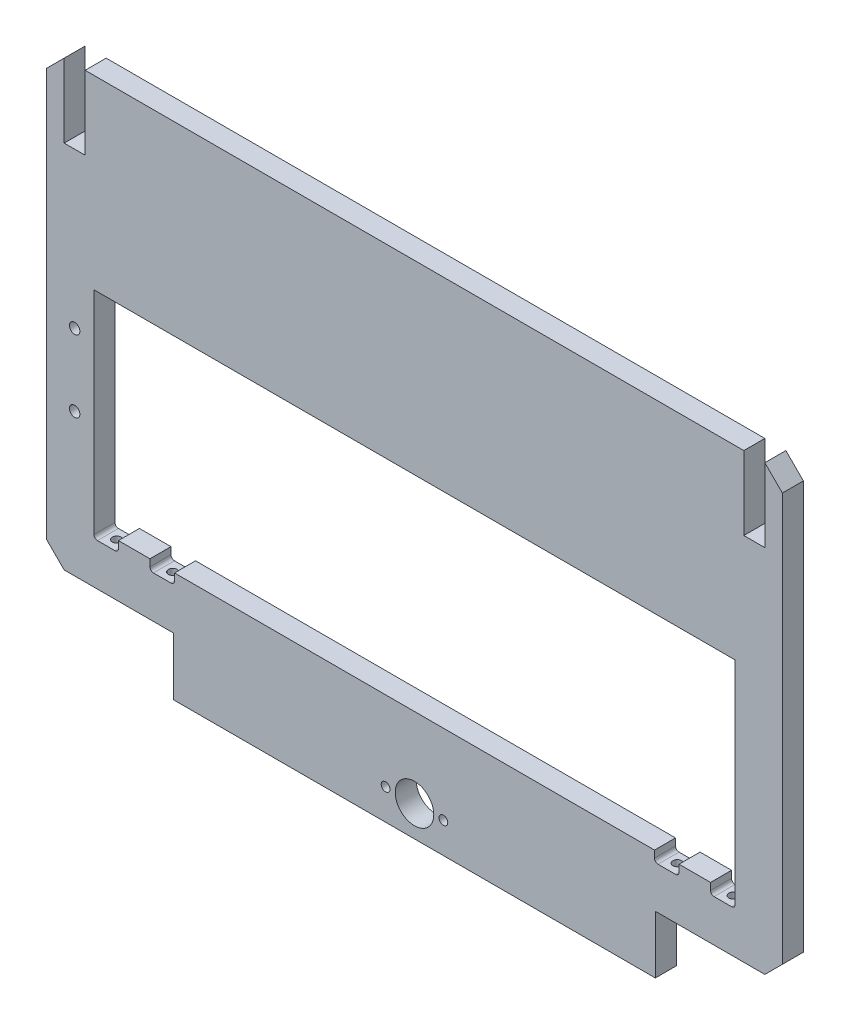
SolidWorks part; units mm, degrees
other "DetailItem1"
other "DetailItem2"
material "Beech"
ref_plane "Front Plane" through (0, 0, 0) normal (0, 0, 1) x (1, 0, 0)
ref_plane "Top Plane" through (0, 0, 0) normal (0, 1, 0) x (1, 0, 0)
ref_plane "Right Plane" through (0, 0, 0) normal (1, 0, 0) x (0, 0, -1)
sketch "Sketch1" plane through (0, 0, 0) normal (0, 0, 1) x (1, 0, 0)
  line L1 (-137.5, -16.5) -> (137.5, -16.5)
  line L2 (-137.5, -16.5) -> (-137.5, 16.5)
  line L3 (-137.5, 16.5) -> (137.5, 16.5)
  line L4 (137.5, -16.5) -> (137.5, 16.5)
  line L5 (-137.5, -16.5) -> (137.5, 16.5) construction
  line L6 (-137.5, 16.5) -> (137.5, -16.5) construction
  point P0 (0, 0)
  dimension "D1" = 275
  dimension "D2" = 33
extrude "Boss-Extrude1" add sketch "Sketch1" along normal blind 12
sketch "Sketch2" plane through (0, 0, 12) normal (0, 0, 1) x (1, 0, 0)
  line L0 (137.5, 16.5) -> (-137.5, 16.5) construction
  line L1 (-16.5, 1) -> (20.0379, 1) construction
  circle A0 centre (0, 1) radius 11
  circle A1 centre (-16.5, 1) radius 2.5
  circle A2 centre (16.5, 1) radius 2.5
  point P2 (0, 16.5)
  dimension "D1" = 15.5
  dimension "D2" = 22
  dimension "D3" = 5
  dimension "D4" = 5
  dimension "D5" = 33
  dimension "D6" = 16.5
extrude "Cut-Extrude1" cut sketch "Sketch2" against normal up to next
sketch "Sketch3" plane through (0, 0, 12) normal (0, 0, 1) x (1, 0, 0)
  line L0 (-137.5, -16.5) -> (137.5, -16.5) construction
  line L1 (-210, 16.5) -> (210, 16.5)
  line L2 (-210, 16.5) -> (-210, 46.5)
  line L3 (-183, 46.5) -> (183, 46.5)
  line L4 (210, 16.5) -> (210, 46.5)
  line L5 (-183, 163.5) -> (183, 163.5)
  line L6 (-210, 46.5) -> (-210, 269.5)
  line L7 (-210, 269.5) -> (210, 269.5)
  line L8 (-183, 46.5) -> (-183, 163.5)
  line L11 (210, 46.5) -> (210, 269.5)
  line L13 (183, 46.5) -> (183, 163.5)
  circle A0 centre (0, 1) radius 11 construction
  dimension "D1" = 30
  dimension "D2" = 420
  dimension "D3" = 210
  dimension "D5" = 286
  dimension "D8" = 117
extrude "Boss-Extrude2" add sketch "Sketch3" against normal blind 12
sketch "Sketch4" plane through (0, 46.5, 0) normal (0, 1, 0) x (1, 0, 0)
  line L0 (-183, -6) -> (183, -6) construction
  line L1 (-183, 0) -> (-183, -12) construction
  line L2 (183, 0) -> (183, -12) construction
  line L4 (183, 0) -> (-183, 0) construction
  circle A0 centre (-144, -6) radius 2.5
  circle A1 centre (-176, -6) radius 2.5
  point P10 (0, 0)
  point P12 (0, 0)
  dimension "D1" = 5
  dimension "D2" = 5
  dimension "D3" = 144
  dimension "D4" = 176
extrude "Cut-Extrude2" cut sketch "Sketch4" against normal up to next
mirror "Mirror1" about plane through (0, 0, 0) normal (1, 0, 0) of "Cut-Extrude2"
sketch "Sketch5" plane through (0, 0, 12) normal (0, 0, 1) x (1, 0, 0)
  line L0 (-183, 46.5) -> (-183, 40.5)
  line L1 (-183, 40.5) -> (-169, 40.5)
  line L2 (-169, 40.5) -> (-169, 46.5)
  line L3 (183, 46.5) -> (-183, 46.5) construction
  line L4 (-169, 46.5) -> (-183, 46.5)
  line L5 (-151, 46.5) -> (-151, 40.5)
  line L6 (-151, 40.5) -> (-137, 40.5)
  line L7 (-137, 40.5) -> (-137, 46.5)
  line L8 (-151, 46.5) -> (-137, 46.5)
  circle A0 centre (0, 1) radius 11 construction
  dimension "D1" = 14
  dimension "D2" = 6
  dimension "D3" = 6
  dimension "D4" = 14
  dimension "D5" = 137
  dimension "D6" = 169
extrude "Cut-Extrude3" cut sketch "Sketch5" against normal up to next
fillet "Fillet1" radius 2 4 edges at (-137, 40.5, 6) (-151, 40.5, 6) (-169, 40.5, 6) (-183, 40.5, 6)
mirror "Mirror2" about plane through (0, 0, 0) normal (1, 0, 0) of "Fillet1", "Cut-Extrude3"
chamfer "Chamfer1" distance 10 angle 45 2 edges at (210, 16.5, 6) (-210, 16.5, 6)
sketch "Sketch6" plane through (0, 0, 12) normal (0, 0, 1) x (1, 0, 0)
  line L0 (-194, 84.613) -> (-194, 177.9433) construction
  line L1 (194, 84.613) -> (194, 173.992) construction
  line L3 (-183, 42.5) -> (-183, 163.5) construction
  line L4 (183, 163.5) -> (183, 42.5) construction
  circle A0 centre (-194, 138.9056) radius 3
  circle A1 centre (-194, 97.8948) radius 3
  dimension "D3" = 6
  dimension "D4" = 6
  dimension "D1" = 11
  dimension "D2" = 11
extrude "Cut-Extrude4" cut sketch "Sketch6" against normal up to next
sketch "Sketch8" plane through (0, 0, 12) normal (0, 0, 1) x (1, 0, 0)
  line L0 (0, 79.2288) -> (0, 236.3795) construction
  line L1 (210, 269.5) -> (-210, 269.5) construction
  line L2 (-188, 269.5) -> (-200, 269.5)
  line L3 (-188, 269.5) -> (-188, 227.5)
  line L4 (-188, 227.5) -> (-200, 227.5)
  line L5 (-200, 269.5) -> (-200, 227.5)
  line L7 (188, 269.5) -> (200, 269.5)
  line L8 (188, 269.5) -> (188, 227.5)
  line L9 (188, 227.5) -> (200, 227.5)
  line L10 (200, 269.5) -> (200, 227.5)
  dimension "D1" = 376
  dimension "D2" = 188
  dimension "D3" = 12
  dimension "D4" = 12
  dimension "D5" = 42
  dimension "D6" = 42
extrude "Cut-Extrude6" cut sketch "Sketch8" against normal up to next
chamfer "Chamfer2" distance 10 angle 45 2 edges at (210, 269.5, 6) (-210, 269.5, 6)
